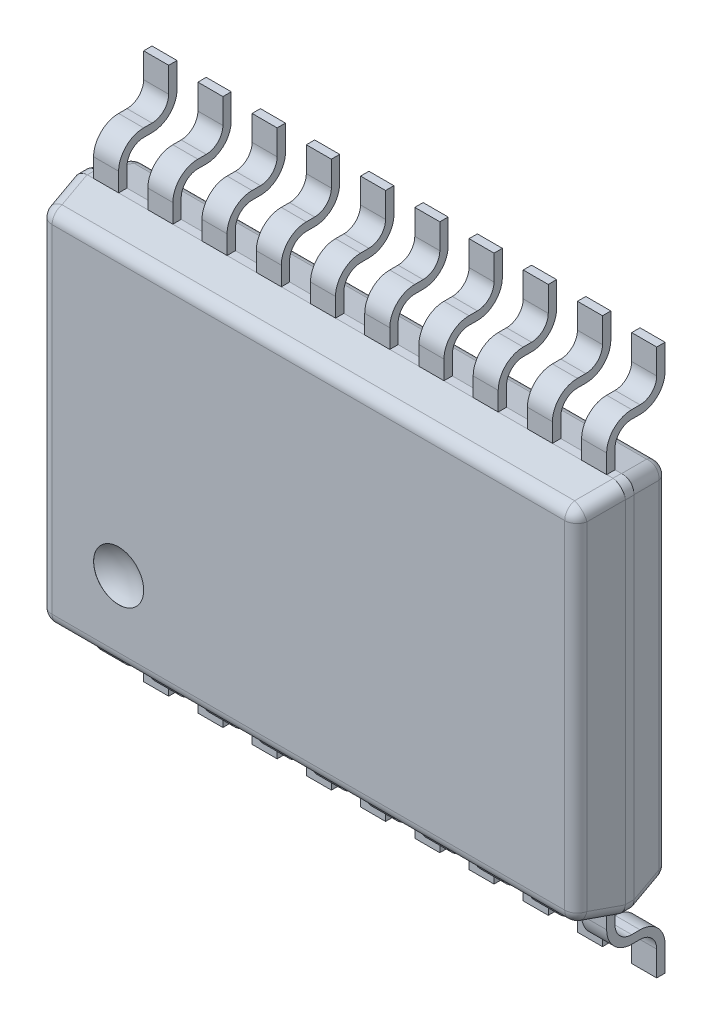
SolidWorks part; units mm, degrees
ref_plane "Front Plane" through (0, 0, 0) normal (0, 0, 1) x (1, 0, 0)
ref_plane "Top Plane" through (0, 0, 0) normal (0, 1, 0) x (1, 0, 0)
ref_plane "Right Plane" through (0, 0, 0) normal (1, 0, 0) x (0, 0, -1)
ref_plane "Plane1" through (0, 0, 0.1) normal (0, 0, 1) x (1, 0, 0)
sketch "Sketch1" plane through (0, 0, 0.1) normal (0, 0, 1) x (1, 0, 0)
  line L1 (-3.3, 2.25) -> (3.3, 2.25)
  line L2 (-3.3, 2.25) -> (-3.3, -2.25)
  line L3 (-3.3, -2.25) -> (3.3, -2.25)
  line L4 (3.3, 2.25) -> (3.3, -2.25)
extrude "Extrude2" add sketch "Sketch1" along normal blind 1.1
chamfer "Chamfer2" distance 0.5 angle 12 4 edges at (3.3, 0, 1.2) (0, -2.25, 1.2) (-3.3, 0, 1.2) (0, 2.25, 1.2) first distance on face at (3.3, 0, 0.65) first distance on face at (0, -2.25, 0.65) first distance on face at (-3.3, 0, 0.65) first distance on face at (0, 2.25, 0.65)
chamfer "Chamfer3" distance 0.5 angle 12 4 edges at (-3.3, 0, 0.1) (0, -2.25, 0.1) (3.3, 0, 0.1) (0, 2.25, 0.1) first distance on face at (-3.3, 0, 0.4) first distance on face at (0, -2.25, 0.4) first distance on face at (3.3, 0, 0.4) first distance on face at (0, 2.25, 0.4)
fillet "Fillet1" radius 0.15 20 edges at (3.2469, -2.1969, 0.35) (-3.2469, 2.1969, 0.35) (3.2469, 2.1969, 0.35) (3.1937, 0, 0.1) (0, -2.1437, 0.1) (-3.1937, 0, 0.1) (0, 2.1437, 0.1) (-3.2469, -2.1969, 0.35) (-3.1937, 0, 1.2) (0, 2.1437, 1.2) (3.1937, 0, 1.2) (0, -2.1437, 1.2) (3.2469, -2.1969, 0.95) (-3.2469, -2.1969, 0.95) (-3.2469, 2.1969, 0.95) (3.2469, 2.1969, 0.95) (3.3, -2.25, 0.65) (3.3, 2.25, 0.65) (-3.3, -2.25, 0.65) (-3.3, 2.25, 0.65)
sketch "Sketch2" plane through (0, 0, 0) normal (0, 0, 1) x (1, 0, 0)
  line L0 (2.425, -2.25) -> (2.125, -2.25)
  line L1 (2.925, -2.25) -> (2.925, -3.275) construction
  line L2 (3.15, -2.25) -> (-3.15, -2.25) construction
  line L3 (3.075, -2.25) -> (2.775, -2.25)
  line L4 (3.075, -2.25) -> (3.075, -3.275)
  line L5 (3.075, -3.275) -> (2.775, -3.275)
  line L6 (2.775, -2.25) -> (2.775, -3.275)
  line L7 (2.425, -2.25) -> (2.425, -3.275)
  line L8 (2.425, -3.275) -> (2.125, -3.275)
  line L9 (2.125, -2.25) -> (2.125, -3.275)
  line L10 (1.775, -2.25) -> (1.475, -2.25)
  line L11 (1.775, -2.25) -> (1.775, -3.275)
  line L12 (1.775, -3.275) -> (1.475, -3.275)
  line L13 (1.475, -2.25) -> (1.475, -3.275)
  line L14 (1.125, -2.25) -> (0.825, -2.25)
  line L15 (1.125, -2.25) -> (1.125, -3.275)
  line L16 (1.125, -3.275) -> (0.825, -3.275)
  line L17 (0.825, -2.25) -> (0.825, -3.275)
  line L18 (0.475, -2.25) -> (0.175, -2.25)
  line L19 (0.475, -2.25) -> (0.475, -3.275)
  line L20 (0.475, -3.275) -> (0.175, -3.275)
  line L21 (0.175, -2.25) -> (0.175, -3.275)
  line L22 (-0.175, -2.25) -> (-0.475, -2.25)
  line L23 (-0.175, -2.25) -> (-0.175, -3.275)
  line L24 (-0.175, -3.275) -> (-0.475, -3.275)
  line L25 (-0.475, -2.25) -> (-0.475, -3.275)
  line L26 (-0.825, -2.25) -> (-1.125, -2.25)
  line L27 (-0.825, -2.25) -> (-0.825, -3.275)
  line L28 (-0.825, -3.275) -> (-1.125, -3.275)
  line L29 (-1.125, -2.25) -> (-1.125, -3.275)
  line L30 (-1.475, -2.25) -> (-1.775, -2.25)
  line L31 (-1.475, -2.25) -> (-1.475, -3.275)
  line L32 (-1.475, -3.275) -> (-1.775, -3.275)
  line L33 (-1.775, -2.25) -> (-1.775, -3.275)
  line L34 (-2.125, -2.25) -> (-2.425, -2.25)
  line L35 (-2.125, -2.25) -> (-2.125, -3.275)
  line L36 (-2.125, -3.275) -> (-2.425, -3.275)
  line L37 (-2.425, -2.25) -> (-2.425, -3.275)
  line L38 (-2.775, -2.25) -> (-3.075, -2.25)
  line L39 (-2.775, -2.25) -> (-2.775, -3.275)
  line L40 (-2.775, -3.275) -> (-3.075, -3.275)
  line L41 (-3.075, -2.25) -> (-3.075, -3.275)
extrude "Extrude3" add sketch "Sketch2" along normal blind 0.7 separate body
sketch "Sketch3" plane through (3.075, 0, 0) normal (1, 0, 0) x (0, 0, -1)
  line L2 (-0.1, -2.975) -> (-0.1, -3.275)
  line L3 (-0.3, -2.775) -> (-0.4, -2.775)
  line L4 (0, -3.275) -> (0, -2.25) construction
  line L6 (-0.7, -3.275) -> (-0.7, -2.25) construction
  line L7 (-0.6, -2.25) -> (0, -2.25)
  line L9 (-0.3, -2.675) -> (-0.4, -2.675)
  line L10 (-0.6, -2.475) -> (-0.6, -2.25)
  line L11 (-0.1, -3.275) -> (-0.7, -3.275)
  line L12 (-0.7, -3.275) -> (-0.7, -2.475)
  line L13 (0, -2.25) -> (0, -2.975)
  line L14 (-0.7, -2.475) -> (-0.7, -2.25) construction
  line L20 (0, -2.975) -> (0, -3.275) construction
  arc A0 (-0.3, -2.675) -> (0, -2.975) centre (-0.3, -2.975) cw
  arc A1 (-0.1, -2.975) -> (-0.3, -2.775) centre (-0.3, -2.975) ccw
  arc A2 (-0.7, -2.475) -> (-0.4, -2.775) centre (-0.4, -2.475) ccw
  arc A4 (-0.6, -2.475) -> (-0.4, -2.675) centre (-0.4, -2.475) ccw
  arc A6 (0, -2.975) -> (-0.3, -2.675) centre (-0.3, -2.975) ccw construction
  point P3 (0, -2.675)
  point P20 (-0.7, -2.775)
extrude "Extrude4" cut sketch "Sketch3" against normal through all
mirror "Mirror1" about plane through (0, 0, 0) normal (0, 1, 0) of "Extrude3", "Extrude4"
sketch "Sketch4" plane through (0, 0, 1.2) normal (0, 0, 1) x (1, 0, 0)
  circle A0 centre (-2.275, -1.225) radius 0.3
extrude "Extrude5" cut sketch "Sketch4" against normal blind 0.001
dome "Dome1" faces to dome 1 distance 0.1 reverse direction yes elliptical dome no face at (-1.975, -1.225, 1.199) parameters "D1"=0.1
